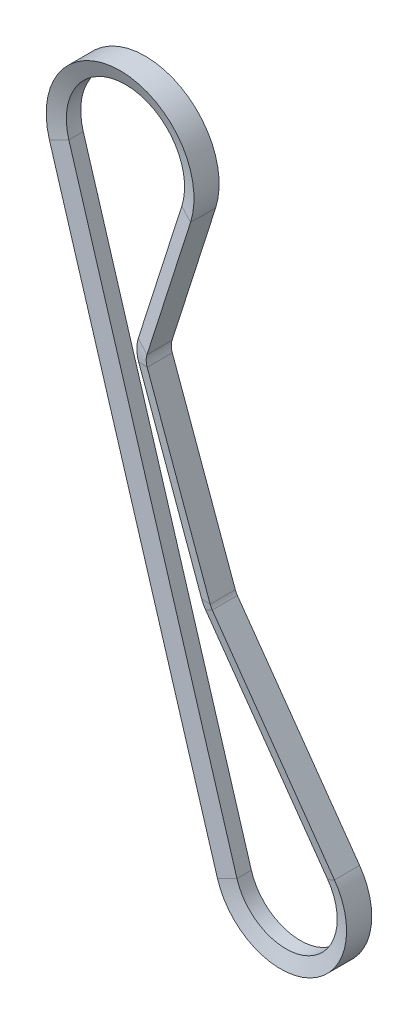
SolidWorks part; units mm, degrees
ref_plane "Front Plane" through (0, 0, 0) normal (0, 0, 1) x (1, 0, 0)
ref_plane "Top Plane" through (0, 0, 0) normal (0, 1, 0) x (1, 0, 0)
ref_plane "Right Plane" through (0, 0, 0) normal (1, 0, 0) x (0, 0, -1)
sketch "Sketch2" plane through (0, 0, 0) normal (0, 0, 1) x (1, 0, 0)
  line L0 (0, 0) -> (1, 0) construction
  line L1 (0, 0) -> (0, 1) construction
  line L12 (-23.9292, -7.2384) -> (-87.6214, 203.3187)
  line L14 (-34.1478, 202.9079) -> (-50.6402, 151.2632)
  line L15 (-50.5606, 147.1663) -> (-26.6921, 81.3613)
  line L16 (-25.9053, 79.8574) -> (20.4041, 14.4454)
  arc A4 (-87.6214, 203.3187) -> (-34.1478, 202.9079) centre (-60.8208, 211.4257) cw
  arc A7 (20.4041, 14.4454) -> (-23.9292, -7.2384) centre (0, 0) cw
  arc A8 (-50.6402, 151.2632) -> (-50.5606, 147.1663) centre (-44.5911, 149.3315) ccw
  arc A9 (-26.6921, 81.3613) -> (-25.9053, 79.8574) centre (-20.7226, 83.5265) ccw
ref_plane "Plane4" through (20.4041, 14.4454, 0) normal (0.5778, -0.8162, 0) x (-0.8162, -0.5778, 0)
sketch "Sketch3" plane through (20.4041, 14.4454, 0) normal (0.5778, -0.8162, 0) x (-0.8162, -0.5778, 0)
  line L0 (0, -4.7625) -> (0, 4.7625)
  line L1 (0, -4.7625) -> (5.588, -2.7286)
  line L2 (5.588, -2.7286) -> (5.588, 2.7286)
  line L3 (5.588, 2.7286) -> (0, 4.7625)
  line L4 (0, 0) -> (5.588, 0) construction
  dimension "D1" = 9.525
  dimension "D2" = 5.588
  dimension "D3" = 40
sweep "Sweep1" add profiles "Sketch3" path "Sketch2"
